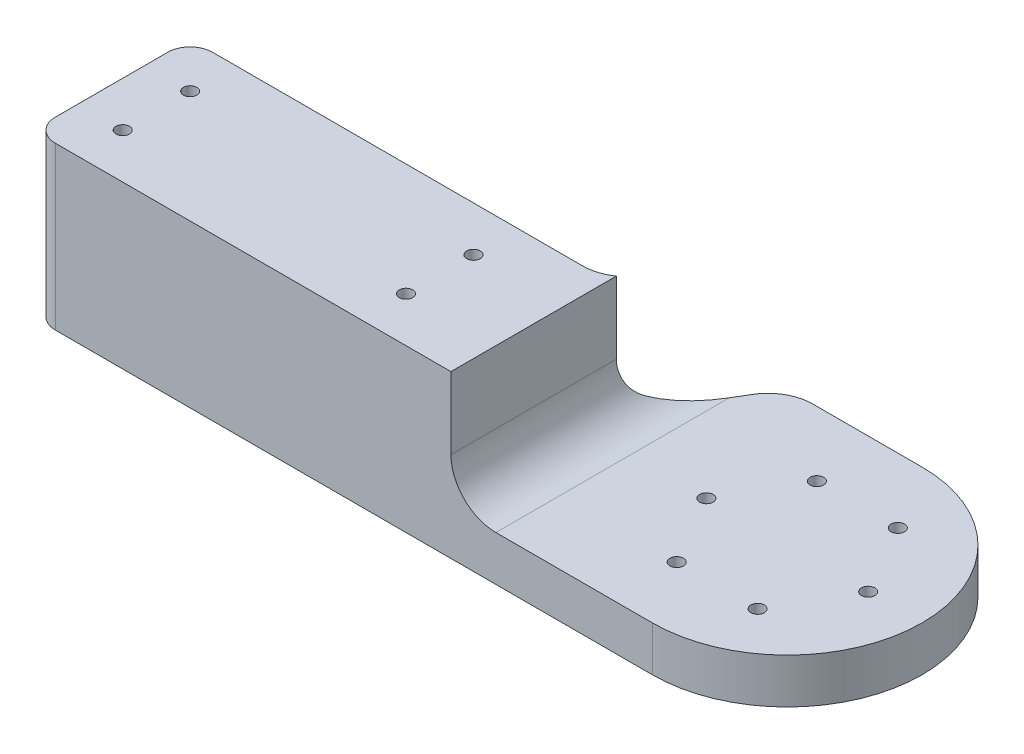
SolidWorks part; units mm, degrees
ref_plane "Front Plane" through (0, 0, 0) normal (1, 0, 0) x (0, 1, 0)
ref_plane "Top Plane" through (0, 0, 0) normal (0, 0, 1) x (0, 1, 0)
ref_plane "Right Plane" through (0, 0, 0) normal (0, 1, 0) x (-1, 0, 0)
sketch "Sketch1" plane through (0, 0, 0) normal (0, 1, 0) x (-1, 0, 0)
  line L0 (0, 35) -> (-44.8, 35)
  line L1 (0, 35) -> (88, 35)
  line L2 (0, 35) -> (0, 0)
  line L3 (0, 0) -> (88, 0)
  line L4 (93, 30) -> (93, 5)
  line L5 (20, 10) -> (83, 10) construction
  line L6 (20, 10) -> (20, 25) construction
  line L7 (20, 25) -> (83, 25) construction
  line L8 (83, 10) -> (83, 25) construction
  line L9 (-44.8, -25) -> (-14.8, -25)
  line L10 (-14.8, -25) -> (0, 0)
  line L11 (-14.8, 35) -> (-14.8, -25) construction
  arc A0 (88, 0) -> (93, 5) centre (88, 5) ccw
  arc A1 (88, 35) -> (93, 30) centre (88, 30) cw
  circle A2 centre (20, 25) radius 1.5
  circle A3 centre (83, 25) radius 1.5
  circle A4 centre (83, 10) radius 1.5
  circle A5 centre (20, 10) radius 1.5
  arc A6 (-44.8, 35) -> (-44.8, -25) centre (-44.8, 5) ccw
  circle A7 centre (-44.8, 5) radius 18 construction
  circle A8 centre (-62.8, 5) radius 1.5
  circle A9 centre (-53.8, 20.5885) radius 1.5
  circle A10 centre (-35.8, 20.5885) radius 1.5
  circle A11 centre (-26.8, 5) radius 1.5
  circle A12 centre (-35.8, -10.5885) radius 1.5
  circle A13 centre (-53.8, -10.5885) radius 1.5
  point P14 (93, 35)
  dimension "D6" = 5
  dimension "D7" = 3
  dimension "D8" = 60
  dimension "D11" = 36
  dimension "D12" = 3
  dimension "D1" = 15
  dimension "D2" = 10
  dimension "HipLength" = 93
  dimension "D3" = 20
  dimension "D4" = 10
  dimension "D5" = 10
  dimension "D9" = 30
  dimension "D10" = 14.8
  dimension "D13" = 6
extrude "Boss-Extrude2" add sketch "Sketch1" against normal blind 10 contours L0 A6 L9 L10 L2 A13 A12 A11 A10 A9 A8 | A1 L1 L2 L3 A0 L4 A5 A4 A3 A2 region at (35.8085, 0, 6.0346) region at (-46.3046, 0, 17.5)
extrude "Boss-Extrude3" add sketch "Sketch1<3>" along normal blind 26 contours A1 L1 L2 L3 A0 L4 A5 A4 A3 A2 region at (-46.3046, 0, 17.5)
sketch "Sketch1<3>" plane through (0, 0, 0) normal (0, 1, 0) x (-1, 0, 0) same geometry as "Sketch1"
fillet "Fillet1" radius 10 3 edges at (0, 0, 17.5) (14.8, -5, -25) (0, -5, 0)
equation "\"MotorDriverLength\"= 60mm"
equation "\"MotorLength\"= 60"
equation "\"MotorDriverWidth\"=44"
equation "\"MotorWidth\"= 37"
equation "\"InnerWallThickness\"=3"
equation "\"BatteryWidth\"= 60"
equation "\"OuterWallThickness\" = 6"
equation "\"CompartmentHeight\"=37"
equation "\"CompartmentWidth\"= \"MotorDriverLength\""
equation "\"MotorDiameter\"=37"
equation "\"BatteryHeight\"=24.2019"
equation "\"MotorDriverHeight\"=28"
equation "\"CircuitHeight\"=30"
equation "\"FanThickness\"= 10"
equation "\"FanHeight\"=50"
equation "\"MotorShaftHole\"=12"
equation "\"BearingBore\"=10"
equation "\"MinShinWidth\"= 20"
equation "\"ShinThickness\"=10"
equation "\"PivotDistance\"=30"
equation "\"ThighLength\"= 150"
equation "\"KneeLength\" =80"
equation "\"HipBore\"=27"
equation "\"ThighThickness\"=10"
equation "\"MaxBending\"=135"
equation "\"MaxStretchingAngle\"= 50"
equation "\"ThighJointDistance\"=157.485"
equation "\"ShinLength\"=120"
equation "\"BearingDiameter\"= 10"
equation "\"CircuitLength\"=50"
equation "\"ChessisInnerWidth\"= \"OuterWallThickness\" * 2 + \"MotorDriverLength\" + \"MotorDiameter\" + \"InnerWallThickness\" * 3 + \"CircuitLength\""
equation "\"ChessisHeight\"= \"BatteryHeight\" + 10 + \"InnerWallThickness\" + \"MotorDiameter\" + 10 + \"OuterWallThickness\" * 2"
equation "\"ChassisWidth\"= \"MotorDriverWidth\"*4+30"
